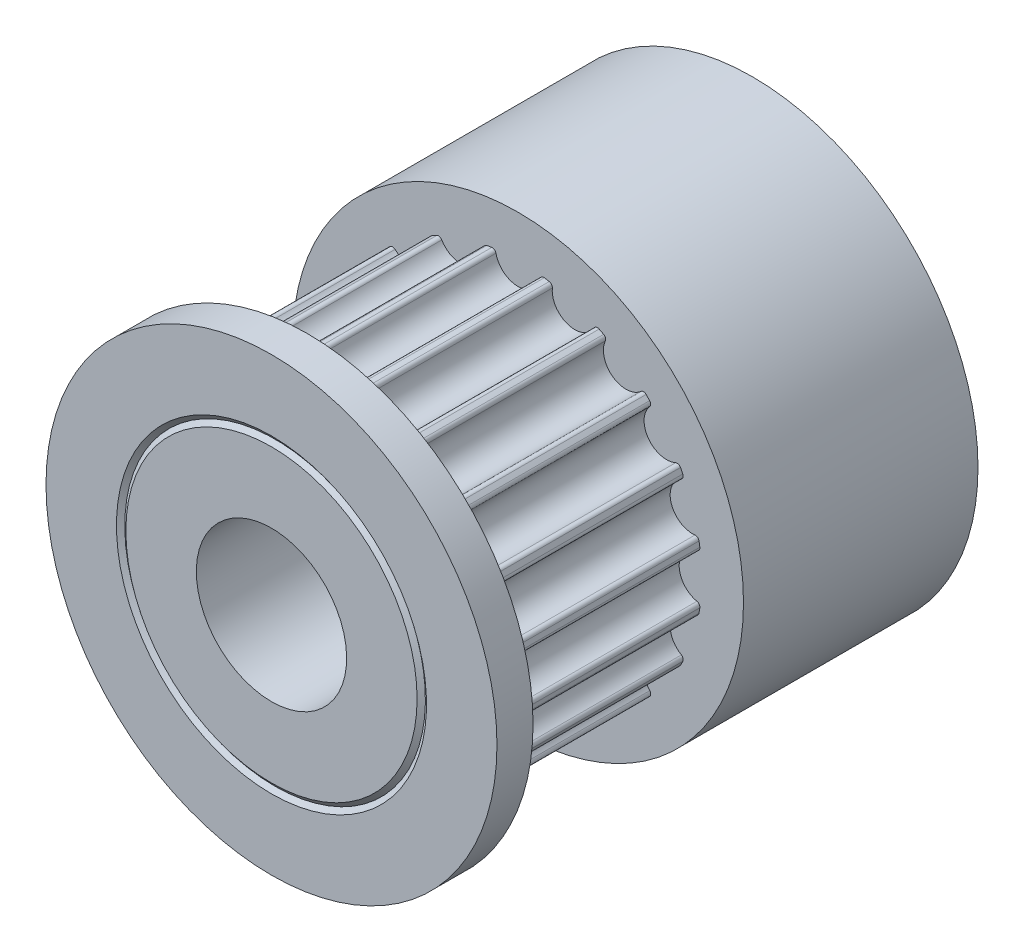
SolidWorks part; units mm, degrees
ref_plane "Front" through (0, 0, 0) normal (0, 0, 1) x (1, 0, 0)
ref_plane "Top" through (0, 0, 0) normal (0, 1, 0) x (1, 0, 0)
ref_plane "Right" through (0, 0, 0) normal (1, 0, 0) x (0, 0, -1)
sketch "Sketch1" plane through (0, 0, 0) normal (1, 0, 0) x (0, 0, -1)
  line L0 (-8.2, 0) -> (7.8, 0) construction
  line L1 (7.8, 7.5) -> (7.8, -7.5) construction
  line L2 (7.8, 2.5) -> (7.8, -2.5) construction
  line L3 (-7, 6.11) -> (-7, -6.11) construction
  line L4 (-8.2, 7.5) -> (-8.2, -7.5) construction
  line L5 (-8.2, 7.5) -> (-7, 7.5) construction
  line L6 (7.8, 7.5) -> (0, 7.5) construction
  line L7 (-7, -6.11) -> (0, -6.11) construction
  line L8 (0, -6.11) -> (0, 0) construction
  line L9 (-6.5, -6.11) -> (-0.5, -6.11) construction
  line L10 (1.9, 7.5) -> (1.9, 2.5) construction
  line L11 (1.9, 2.5) -> (5.9, 2.5) construction
  line L12 (5.9, 2.5) -> (5.9, 7.5) construction
  line L13 (3.9, 7.5) -> (3.9, 2.5) construction
  line L14 (0, 7.5) -> (0, 0) construction
  line L15 (5.9758, 8.1562) -> (5.3696, 7.8062) construction
  line L16 (5.3696, 7.8062) -> (5.9758, 7.4562) construction
  line L17 (5.9758, 7.4562) -> (5.9758, 8.1562) construction
  line L18 (5.3696, 7.8062) -> (5.4453, 7.8062) construction
  line L19 (5.4453, 7.85) -> (5.4453, 7.7625) construction
  line L20 (5.9, 7.8062) -> (5.9758, 7.8062) construction
  line L21 (5.9, 8.1125) -> (5.9, 7.5) construction
  line L22 (5.9379, 7.8062) -> (5.9379, 7.4781) construction
  line L23 (-8.2, -7.5) -> (7.8, -7.5) construction
  point P3 (-7, 0)
  point P4 (3.9, 7.5)
  point P13 (-8.2, 2.5)
  point P15 (-3.5, -6.11)
  point P19 (-6.5, -6.11)
  point P20 (-0.5, -6.11)
  point P27 (-3.5, -6.11)
  point P30 (7.8, -2.5)
  point P40 (-0.2, -7.5)
  point P49 (0, 0)
  dimension "Overall Width" = 16
  dimension "OD" = 15
  dimension "Pitch Diameter" = 12.22
  dimension "For Shaft Diameter" = 5
  dimension "For Maximum Belt Width" = 6
  dimension "Inside Width" = 7
  dimension "Hub Diameter" = 15
  dimension "Set Screw Center" = 3.9
  dimension "Set screw Diameter" = 4
  dimension "Hub Length" = 7.8
  dimension "Outside Width" = 8.2
  dimension "Thread Pitch" = 0.7
  dimension "D1" = 0.0875
  dimension "D2" = 1.2
sketch "Sketch11" plane through (0, 0, 0) normal (0, 0, 1) x (1, 0, 0)
  line L0 (0, 0) -> (-0.7486, 6.064) construction
  line L1 (0, 0) -> (0.7486, 6.064) construction
  line L2 (0, 0) -> (0, 5.36) construction
  line L3 (-6.11, 0) -> (0, 0) construction
  line L4 (0, 6.11) -> (-6.11, 0) construction
  line L5 (0, 6.86) -> (0, 0) construction
  line L6 (0, 6.11) -> (-2, 6.11)
  arc A0 (-0.7486, 6.064) -> (0.7486, 6.064) centre (0, 6.11) ccw
  circle A1 centre (0, 0) radius 6.11 construction
  circle A2 centre (0, 6.11) radius 0.75 construction
  circle A3 centre (1.8881, 5.811) radius 0.75 construction
  circle A4 centre (3.5914, 4.9431) radius 0.75 construction
  circle A5 centre (4.9431, 3.5914) radius 0.75 construction
  circle A6 centre (5.811, 1.8881) radius 0.75 construction
  circle A7 centre (6.11, 0) radius 0.75 construction
  circle A8 centre (5.811, -1.8881) radius 0.75 construction
  circle A9 centre (4.9431, -3.5914) radius 0.75 construction
  circle A10 centre (3.5914, -4.9431) radius 0.75 construction
  circle A11 centre (1.8881, -5.811) radius 0.75 construction
  circle A12 centre (0, -6.11) radius 0.75 construction
  circle A13 centre (-1.8881, -5.811) radius 0.75 construction
  circle A14 centre (-3.5914, -4.9431) radius 0.75 construction
  circle A15 centre (-4.9431, -3.5914) radius 0.75 construction
  circle A16 centre (-5.811, -1.8881) radius 0.75 construction
  circle A17 centre (-6.11, 0) radius 0.75 construction
  circle A18 centre (-5.811, 1.8881) radius 0.75 construction
  circle A19 centre (-4.9431, 3.5914) radius 0.75 construction
  circle A20 centre (-3.5914, 4.9431) radius 0.75 construction
  circle A21 centre (-1.8881, 5.811) radius 0.75 construction
  point P45 (0, 0)
  point P48 (0, 6.86)
  point P49 (-6.11, 0)
  dimension "Tooth OD" = 1.5
  dimension "Pitch" = 2
  dimension "Number of Teeth" = 20
sketch "Sketch3" plane through (0, 0, 0) normal (1, 0, 0) x (0, 0, -1)
  line L0 (-8.2, 5.1564) -> (-8.08, 5)
  line L1 (-8.08, 5) -> (-8.2, 4.8436)
  line L2 (-7, 6.11) -> (-7, 2.5) construction
  line L3 (-8.2, 4.8436) -> (-8.2, 2.5)
  line L4 (-8.2, 7.5) -> (-8.2, 5.1564)
  line L5 (-8.2, 7.5) -> (-7, 7.5)
  line L6 (-7, 7.5) -> (-7, 6.11)
  line L7 (-7, 6.11) -> (0, 6.11)
  line L8 (0, 6.11) -> (0, 7.5)
  line L9 (0, 7.5) -> (7.8, 7.5)
  line L10 (7.68, 5) -> (7.8, 4.8436)
  line L11 (7.8, 2.5) -> (-8.2, 2.5)
  line L13 (-8.2, 5) -> (-8.08, 5) construction
  line L14 (-8.2, 5.1564) -> (-8.2, 5) construction
  line L15 (-8.2, 5) -> (-8.2, 4.8436) construction
  line L16 (-0.2, -7.5) -> (-0.2, 0) construction
  line L17 (-8.2, 0) -> (7.8, 0) construction
  line L18 (7.8, 5.1564) -> (7.68, 5)
  line L19 (7.8, 5.1564) -> (7.8, 7.5)
  line L20 (7.8, 4.8436) -> (7.8, 2.5)
  point P5 (-7, 4.305)
  dimension "D2" = 2.5
  dimension "D1" = 0.12
  dimension "D3" = 105
revolve "Revolve1" add sketch "Sketch3" angle 360 about L0
sketch "Sketch4" plane through (0, 0, 0) normal (0, 1, 0) x (1, 0, 0)
  line L0 (0, -8.2) -> (0, 7.8) construction
  line L1 (0, 7.8) -> (0, 0) construction
  circle A0 centre (0, 3.9) radius 2
extrude "Cut-Extrude1" [suppressed] cut sketch "Sketch4" along normal through all
sketch "Sketch5" [suppressed] plane through (0, 0, 0) normal (0, 1, 0) x (1, 0, 0)
  circle A2 centre (0, 3.9) radius 2.0001
  circle A3 centre (0, 3.9) radius 2.0001
  dimension "D1" = 0.0001
ref_plane "Plane1" [suppressed] through (0, 7.5, 0) normal (0, 1, 0) x (0, 0, 1)
sketch "Sketch7" [suppressed] plane through (0, 7.5, 0) normal (0, 1, 0) x (0, 0, 1)
  line L0 (-7.8, 0) -> (0, 0) construction
  line L1 (-2.7452, 0) -> (-3.3226, 1) construction
  line L2 (-3.3226, 1) -> (-4.4774, 1) construction
  line L3 (-4.4774, 1) -> (-5.0548, 0) construction
  line L4 (-5.0548, 0) -> (-4.4774, -1) construction
  line L5 (-4.4774, -1) -> (-3.3226, -1) construction
  line L6 (-3.3226, -1) -> (-2.7452, 0) construction
  line L7 (-3.9, -2.0001) -> (-3.9, -1) construction
  line L8 (-3.9, -1) -> (-3.9, 0) construction
  circle A0 centre (-3.9, 0) radius 2.0001 construction
  circle A1 centre (-3.9, 0) radius 2.0001
  circle A2 centre (-3.9, 0) radius 1 construction
  circle A3 centre (-3.9, 0) radius 1.5001 construction
  point P15 (-3.9, -1.5001)
extrude "Boss-Extrude1" [suppressed] add sketch "Sketch7" against normal up to vertex separate body
sketch "Sketch13" [suppressed] plane through (0, 7.5, 0) normal (0, 1, 0) x (1, 0, 0)
  circle A0 centre (0, 3.9) radius 1.5001
  circle A1 centre (0, 3.9) radius 1.5001 construction
extrude "Cut-Extrude4" [suppressed] cut sketch "Sketch13" along normal blind 2 and the other way blind 10 draft 60 from offset 2 offset against normal yes
sketch "Sketch14" [suppressed] plane through (0, 7.5, 0) normal (0, 1, 0) x (1, 0, 0)
  line L0 (-1, 3.3226) -> (0, 2.7452) construction
  line L1 (-1, 4.4774) -> (-1, 3.3226) construction
  line L2 (0, 5.0548) -> (-1, 4.4774) construction
  line L3 (1, 4.4774) -> (0, 5.0548) construction
  line L4 (1, 3.3226) -> (1, 4.4774) construction
  line L5 (0, 2.7452) -> (1, 3.3226) construction
  line L6 (-1, 3.3226) -> (0, 2.7452)
  line L7 (-1, 4.4774) -> (-1, 3.3226)
  line L8 (0, 5.0548) -> (-1, 4.4774)
  line L9 (1, 4.4774) -> (0, 5.0548)
  line L10 (1, 3.3226) -> (1, 4.4774)
  line L11 (0, 2.7452) -> (1, 3.3226)
  circle A0 centre (0, 3.9) radius 1.5001 construction
  circle A1 centre (0, 3.9) radius 1.5001
extrude "Boss-Extrude2" [suppressed] add sketch "Sketch14" against normal up to vertex
sketch "Sketch15" [suppressed] plane through (0, 7.5, 0) normal (0, 1, 0) x (1, 0, 0)
  circle A0 centre (0, 3.9) radius 1.1548
extrude "Cut-Extrude7" [suppressed] cut sketch "Sketch15" against normal blind 2 draft 45
chamfer "Chamfer4" [suppressed] distance 0.5 angle 45
chamfer "Chamfer1" [suppressed] distance 0.3 angle 45
chamfer "Chamfer2" [suppressed] distance 0.3 angle 45
pattern_circular "CirPattern3" [suppressed] count 2 over 90 about axis through (0, 0, 8.2) along (0, 0, -1) of bodies 109
sketch "Sketch10" plane through (0, 0, 0) normal (0, 0, 1) x (1, 0, 0)
  line L0 (-0.75, 6.11) -> (0.75, 6.11) construction
  line L1 (0, 0) -> (0, 6.11) construction
  line L2 (2.5, 0) -> (-2.5, 0) construction
  line L3 (-7.5, 0) -> (7.5, 0) construction
  circle A1 centre (0, 6.11) radius 0.75
  circle A4 centre (0, 0) radius 6.11 construction
  circle A5 centre (0, 0) radius 6.11 construction
  circle A6 centre (0, 0) radius 7.5 construction
  circle A7 centre (0, 0) radius 2.5 construction
  dimension "D1" = 1.5
extrude "Cut-Extrude3" cut sketch "Sketch10" along normal up to surface (7 mm away) up to face at (0, -7.5, 7)
fillet "Fillet3" radius 0.125 2 edges at (0.7486, 6.064, 3.5) (-0.7486, 6.064, 3.5)
pattern_circular "CirPattern2" count 20 over 360 about axis through (0, 0, 0) along (0, 0, 1) of "Cut-Extrude3", "Fillet3"
chamfer "Chamfer3" [suppressed] distance 0.23 angle 45
pattern_circular "CirPattern4" [suppressed] count 2 over 90 about axis through (0, 0, 8.2) along (0, 0, -1) of bodies 118
delete or keep bodies "Body-Delete/Keep 1" [suppressed] bodies 120
sketch "Sketch16" [suppressed] plane through (0, 7.5, 0) normal (0, 1, 0) x (1, 0, 0)
  circle A0 centre (0, 3.9) radius 2
curve "Helix/Spiral1" [suppressed] pitch 0.7 height 6 turns 8.5714
sketch "Sketch17" [suppressed] plane through (0, 0, 0) normal (1, 0, 0) x (0, 0, -1)
  line L0 (5.9379, 7.4781) -> (5.9379, 8.1344)
  line L1 (5.9379, 8.1344) -> (5.4453, 7.85)
  line L2 (5.4453, 7.85) -> (5.4453, 7.7625)
  line L3 (5.4453, 7.7625) -> (5.9379, 7.4781)
  line L4 (5.9758, 8.1562) -> (5.3696, 7.8062) construction
sweep "Cut-Sweep1" [suppressed] cut profiles "Sketch17" path "Helix/Spiral1"
pattern_circular "CirPattern5" [suppressed] count 2 over 90 about axis through (0, 0, 8.2) along (0, 0, -1) of bodies 121
equation "\"Tooth OD@Sketch11\"=\"D1@Sketch10\""
equation "\"D1@Chamfer4\" = \"Set screw Diameter@Sketch1\" / 8"
equation "\"D2@Sketch3\" = ( \"OD@Sketch1\" - \"For Shaft Diameter@Sketch1\" ) / 4"
equation "\"D1@Sketch1\"=\"Thread Pitch@Sketch1\"/8"
equation "\"Number of Teeth@CirPattern2\"=\"Number of Teeth@Sketch11\""
